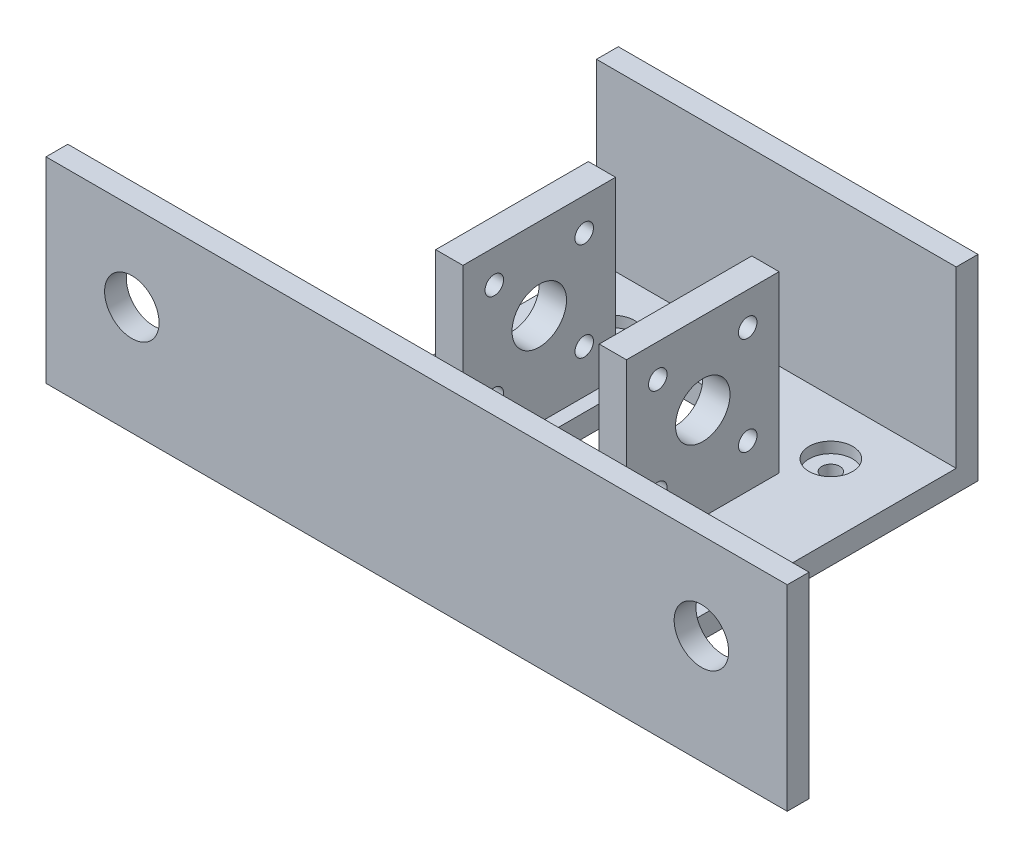
SolidWorks part; units mm, degrees
ref_plane "Front Plane" through (0, 0, 0) normal (0, 0, 1) x (1, 0, 0)
ref_plane "Top Plane" through (0, 0, 0) normal (0, 1, 0) x (1, 0, 0)
ref_plane "Right Plane" through (0, 0, 0) normal (1, 0, 0) x (0, 0, -1)
sketch "Sketch1" plane through (0, 0, 0) normal (0, 1, 0) x (1, 0, 0)
  line L0 (0, 0) -> (0, -14.43) construction
  line L1 (-37.5, 20) -> (37.5, 20)
  line L2 (-37.5, 20) -> (-37.5, -20)
  line L3 (-37.5, -20) -> (37.5, -20)
  line L4 (37.5, 20) -> (37.5, -20)
  line L5 (-37.5, 20) -> (37.5, -20) construction
  line L6 (-37.5, -20) -> (37.5, 20) construction
  line L7 (0, 0) -> (6.508, 0) construction
  line L8 (-5, 10) -> (5, 10)
  line L9 (-5, 10) -> (-5, -10)
  line L10 (-5, -10) -> (5, -10)
  line L11 (5, 10) -> (5, -10)
  line L12 (-5, 10) -> (5, -10) construction
  line L13 (-5, -10) -> (5, 10) construction
  circle A0 centre (-21, 0) radius 5
  circle A1 centre (-30, 8.25) radius 1.7
  circle A2 centre (-12, 8.25) radius 1.7
  circle A3 centre (-12, -8.25) radius 1.7
  circle A4 centre (-30, -8.25) radius 1.7
  circle A5 centre (12, 8.25) radius 1.7
  circle A6 centre (12, -8.25) radius 1.7
  circle A7 centre (21, 0) radius 5
  circle A8 centre (30, -8.25) radius 1.7
  circle A9 centre (30, 8.25) radius 1.7
  point P0 (0, 0)
  dimension "D3" = 10
  dimension "D4" = 16.5
  dimension "D5" = 16.5
  dimension "D6" = 18
  dimension "D9" = 10
  dimension "D11" = 20
  dimension "D13" = 7.5
  dimension "D17" = 3.4
  dimension "D19" = 11.75
  dimension "D20" = 11.75
  dimension "D1" = 75
  dimension "D2" = 40
  dimension "D10" = 10
  dimension "D7" = 2
  dimension "D8" = 2
extrude "Boss-Extrude1" add sketch "Sketch1" along normal blind 3
sketch "Sketch2" plane through (0, 3, 0) normal (0, 1, 0) x (1, 0, 0)
  line L0 (-37.5, 20) -> (-37.5, -20) construction
  line L1 (-33.5, 14) -> (33.5, 14)
  line L2 (-33.5, 14) -> (-33.5, -14)
  line L3 (-33.5, -14) -> (33.5, -14)
  line L4 (33.5, 14) -> (33.5, -14)
  line L5 (37.5, -20) -> (37.5, 20) construction
  line L6 (37.5, 20) -> (-37.5, 20) construction
  line L7 (-37.5, -20) -> (37.5, -20) construction
  dimension "D1" = 4
  dimension "D2" = 4
  dimension "D3" = 6
  dimension "D4" = 6
extrude "Cut-Extrude1" cut sketch "Sketch2" against normal through all both and the other way through all
sketch "Sketch3" plane through (0, 3, 0) normal (0, 1, 0) x (1, 0, 0)
  line L1 (37.5, 20) -> (-37.5, 20)
  line L2 (37.5, 20) -> (37.5, 35)
  line L3 (37.5, 35) -> (-37.5, 35)
  line L4 (-37.5, 20) -> (-37.5, 35)
  line L5 (-37.5, -20) -> (37.5, -20)
  line L6 (-37.5, -20) -> (-37.5, -35)
  line L7 (-37.5, -35) -> (37.5, -35)
  line L8 (37.5, -20) -> (37.5, -35)
  line L10 (-37.5, 20) -> (-33.5, 20)
  line L11 (-37.5, 20) -> (-37.5, -20)
  line L12 (-37.5, -20) -> (-33.5, -20)
  line L13 (-33.5, 20) -> (-33.5, -20)
  line L14 (37.5, 20) -> (33.5, 20)
  line L15 (37.5, 20) -> (37.5, -20)
  line L16 (37.5, -20) -> (33.5, -20)
  line L17 (33.5, 20) -> (33.5, -20)
  line M3 (-33.5, -14) -> (-33.5, 14)
  line M5 (33.5, 14) -> (33.5, -14)
  line M11 (37.5, -20) -> (37.5, 20)
  line M12 (37.5, 20) -> (-37.5, 20)
  line M13 (-37.5, 20) -> (-37.5, -20)
  line M14 (-37.5, -20) -> (37.5, -20)
  dimension "D1" = 15
  dimension "D2" = 15
extrude "Boss-Extrude3" add sketch "Sketch3" along normal blind 110 and the other way blind 3 contours L8 L5 L6 L7 M14 | L4 L1 L2 L3 M12 | L17 M12 M5 M14 M11 | L13 L1 M13 M14 M3 region at (35.5, 3, 0) region at (0, 3, -27.5) region at (0, 3, 27.5) region at (-35.5, 3, 0)
sketch "Sketch6" plane through (0, 3, 0) normal (0, 1, 0) x (1, 0, 0)
  line L0 (-37.5, -35) -> (37.5, -35) construction
  line L1 (-33.5, -20) -> (33.5, -20)
  line L2 (-33.5, -20) -> (-33.5, -31)
  line L3 (-33.5, -31) -> (33.5, -31)
  line L4 (33.5, -20) -> (33.5, -31)
  line L5 (33.5, 20) -> (-33.5, 20)
  line L6 (33.5, 20) -> (33.5, 31)
  line L7 (33.5, 31) -> (-33.5, 31)
  line L8 (-33.5, 20) -> (-33.5, 31)
  line L9 (37.5, 35) -> (-37.5, 35) construction
  dimension "D1" = 4
  dimension "D2" = 4
extrude "Cut-Extrude4" cut sketch "Sketch6" along normal through all
sketch "Sketch7" plane through (-37.5, 0, 0) normal (-1, 0, 0) x (0, 0, 1)
  line L0 (35, 0) -> (35, 113) construction
  line L1 (-35, 113) -> (35, 113)
  line L2 (-35, 113) -> (-35, 76)
  line L3 (-35, 76) -> (35, 76)
  line L4 (35, 113) -> (35, 76)
  dimension "D1" = 37
extrude "Boss-Extrude4" add sketch "Sketch7" along normal blind 45
ref_plane "Plane1" through (0, 0, 0) normal (1, 0, 0) x (0, 0, -1)
mirror "Mirror2" about plane through (0, 0, 0) normal (1, 0, 0) of "Boss-Extrude4"
sketch "Sketch8" plane through (0, 113, 0) normal (0, 1, 0) x (1, 0, 0)
  line L0 (-82.5, -35) -> (-82.5, 35) construction
  line L1 (-33.5, 31) -> (-78.5, 31)
  line L2 (-33.5, 31) -> (-33.5, -31)
  line L3 (-33.5, -31) -> (-78.5, -31)
  line L4 (-78.5, 31) -> (-78.5, -31)
  line L5 (33.5, -31) -> (78.5, -31)
  line L6 (33.5, -31) -> (33.5, 31)
  line L7 (33.5, 31) -> (78.5, 31)
  line L8 (78.5, -31) -> (78.5, 31)
  line L9 (82.5, -35) -> (82.5, 35) construction
  dimension "D1" = 4
  dimension "D2" = 4
extrude "Cut-Extrude6" cut sketch "Sketch8" against normal blind 29
sketch "Sketch9" plane through (-82.5, 0, 0) normal (-1, 0, 0) x (0, 0, 1)
  line L18 (-31, 84) -> (31, 84) construction
  line L19 (-19, 84) -> (19, 84)
  line L20 (-19, 84) -> (-19, 112.5)
  line L21 (-19, 112.5) -> (19, 112.5)
  line L22 (19, 84) -> (19, 112.5)
  line L25 (-31, 84) -> (-31, 113) construction
  dimension "D1" = 38
  dimension "D2" = 12
  dimension "D3" = 28.5
sketch "Sketch11" plane through (0, 0, 35) normal (0, 0, 1) x (1, 0, 0)
  line L0 (82.5, 76) -> (82.5, 113) construction
  line L1 (-82.5, 76) -> (-37.5, 76)
  line L2 (-82.5, 76) -> (-82.5, 80)
  line L3 (-82.5, 80) -> (-37.5, 80)
  line L4 (-37.5, 76) -> (-37.5, 80)
  line L5 (37.5, 76) -> (82.5, 76)
  line L6 (37.5, 76) -> (37.5, 80)
  line L7 (37.5, 80) -> (82.5, 80)
  line L8 (82.5, 76) -> (82.5, 80)
  line L11 (-78.5, 84) -> (-33.5, 84) construction
  line L12 (33.5, 84) -> (78.5, 84) construction
  dimension "D1" = 4
  dimension "D2" = 4
extrude "Cut-Extrude9" cut sketch "Sketch11" against normal through all
extrude "Cut-Extrude10" cut sketch "Sketch9" against normal through all
sketch "Sketch13" plane through (0, 84, 0) normal (0, 1, 0) x (1, 0, 0)
  line L0 (-78.5, 31) -> (-78.5, -31) construction
  line L1 (-41.5, 19) -> (-36.5, 19)
  line L2 (-41.5, 19) -> (-41.5, -19)
  line L3 (-41.5, -19) -> (-36.5, -19)
  line L4 (-36.5, 19) -> (-36.5, -19)
  line L7 (78.5, 31) -> (-78.5, 31) construction
  line L13 (-41.5, -19) -> (-41.5, 19)
  line L17 (-82.5, -19) -> (-107.5, -19)
  line L18 (-82.5, -19) -> (-82.5, 19)
  line L19 (-82.5, 19) -> (-107.5, 19)
  line L20 (-107.5, -19) -> (-107.5, 19)
  line L21 (-107.5, 19) -> (-61, 19)
  line L22 (-107.5, 19) -> (-107.5, -19)
  line L23 (-107.5, -19) -> (-61, -19)
  line L24 (-61, 19) -> (-61, -19)
  dimension "D1" = 37
  dimension "D2" = 5
  dimension "D3" = 38
  dimension "D4" = 12
  dimension "D5" = 25
  dimension "D6" = 46.5
extrude "Boss-Extrude5" add sketch "Sketch13" along normal blind 32 contours L4 L1 L2 L3 region at (-39, 84, 0)
sketch "Sketch14" plane through (-41.5, 0, 0) normal (-1, 0, 0) x (0, 0, 1)
  line L0 (-19, 116) -> (-19, 84) construction
  line L4 (19, 112.5) -> (-19, 112.5) construction
  circle A0 centre (0, 101) radius 5
  circle A1 centre (-8.25, 110) radius 1.7
  circle A2 centre (8.25, 110) radius 1.7
  circle A3 centre (8.25, 92) radius 1.7
  circle A4 centre (-8.25, 92) radius 1.7
  dimension "D1" = 19
  dimension "D2" = 8.25
  dimension "D3" = 10
  dimension "D6" = 3.4
  dimension "D7" = 11.5
  dimension "D8" = 18
  dimension "D9" = 16.5
  dimension "D10" = 9
  dimension "D11" = 8.25
  dimension "D4" = 2
  dimension "D5" = 2
extrude "Cut-Extrude11" cut sketch "Sketch14" against normal blind 32
mirror "Mirror4" about plane through (0, 0, 0) normal (1, 0, 0) of "Boss-Extrude5", "Cut-Extrude11"
sketch "Sketch15" plane through (0, 113, 0) normal (0, 1, 0) x (1, 0, 0)
  line L1 (-82.5, 35) -> (82.5, 35)
  line L2 (-82.5, 35) -> (-82.5, -35)
  line L3 (-82.5, -35) -> (82.5, -35)
  line L4 (82.5, 35) -> (82.5, -35)
  line L5 (-78.5, 31) -> (78.5, 31)
  line L6 (-78.5, 31) -> (-78.5, -31)
  line L7 (-78.5, -31) -> (78.5, -31)
  line L8 (78.5, 31) -> (78.5, -31)
extrude "Boss-Extrude6" add sketch "Sketch15" along normal blind 3
sketch "Sketch16" plane through (0, 0, 35) normal (0, 0, 1) x (1, 0, 0)
  line L1 (-10, 14.0464) -> (10, 14.0464)
  line L2 (-10, 14.0464) -> (-10, 9.2258)
  line L3 (-10, 9.2258) -> (10, 9.2258)
  line L4 (10, 14.0464) -> (10, 9.2258)
  line L5 (-37.5, 0) -> (-37.5, 80) construction
  dimension "D1" = 20
  dimension "D2" = 27.5
extrude "Cut-Extrude12" cut sketch "Sketch16" against normal through all
sketch "Sketch18" plane through (0, 0, 35) normal (0, 0, 1) x (1, 0, 0)
  line L0 (41.5, 116) -> (41.5, 84) construction
  line L2 (33.5, 84) -> (78.5, 84) construction
  circle A0 centre (52.25, 100) radius 5
  dimension "D1" = 10.75
  dimension "D2" = 16
  dimension "D3" = 10
extrude "Cut-Extrude14" cut sketch "Sketch18" against normal through all
mirror "Mirror5" about plane through (0, 0, 0) normal (1, 0, 0) of "Cut-Extrude14"
mirror "Mirror6" about plane through (0, 116, 0) normal (0, 1, 0) of "Mirror4"
sketch "Sketch19" plane through (82.5, 0, 0) normal (1, 0, 0) x (0, 0, -1)
  line L0 (19, 148) -> (19, 84) construction
  line L1 (-19, 112.5) -> (19, 112.5)
  line L2 (-19, 112.5) -> (-19, 116)
  line L3 (-19, 116) -> (19, 116)
  line L4 (19, 112.5) -> (19, 116)
extrude "Cut-Extrude15" cut sketch "Sketch19" against normal blind 10
mirror "Mirror7" about plane through (0, 0, 0) normal (1, 0, 0) of "Cut-Extrude15"
sketch "Sketch20" plane through (0, 3, 0) normal (0, 1, 0) x (1, 0, 0)
  line L0 (33.5, 31) -> (-33.5, 31) construction
  line L1 (-5, -10) -> (5, -10)
  line L2 (-5, -10) -> (-5, 10)
  line L3 (-5, 10) -> (5, 10)
  line L4 (5, -10) -> (5, 10)
  line L5 (-5, -10) -> (5, 10) construction
  line L6 (-5, 10) -> (5, -10) construction
  line L7 (0, 0) -> (0, 17.5) construction
  line L8 (-37.5, 20) -> (37.5, 20)
  line L9 (-37.5, 20) -> (-37.5, -20)
  line L10 (-37.5, -20) -> (37.5, -20)
  line L11 (37.5, 20) -> (37.5, -20)
  line L12 (-37.5, 20) -> (37.5, -20) construction
  line L13 (-37.5, -20) -> (37.5, 20) construction
  line L14 (0, -34.1) -> (0, 34.1) construction
  circle A1 centre (-12, 17.5) radius 1.2
  circle A2 centre (-12, -17.5) radius 1.2
  circle A3 centre (-24, -17.5) radius 1.2
  circle A4 centre (-24, 17.5) radius 1.2
  circle A5 centre (12, -17.5) radius 1.2
  circle A6 centre (24, -17.5) radius 1.2
  circle A7 centre (12, 17.5) radius 1.2
  circle A8 centre (24, 17.5) radius 1.2
  point P2 (0, 0)
  point P10 (0, 0)
  dimension "D1" = 7
  dimension "D2" = 10
  dimension "D4" = 2.5
  dimension "D7" = 35
  dimension "D8" = 7
  dimension "D9" = 2.4
  dimension "D11" = 12
  dimension "D3" = 21
  dimension "D5" = 75
  dimension "D6" = 40
  dimension "D10" = 2
extrude "Cut-Extrude16" cut sketch "Sketch20" against normal blind 10 contours A4 | A1 | A7 | A3 | A2 | A8 | A5 | A6 region at (-12, 3, -17.5) region at (-12, 3, 17.5) region at (-24, 3, 17.5) region at (-24, 3, -17.5) region at (12, 3, 17.5) region at (24, 3, 17.5) region at (12, 3, -17.5) region at (24, 3, -17.5)
sketch "Sketch21" plane through (0, 0, 35) normal (0, 0, 1) x (1, 0, 0)
  line L0 (0, -34.1) -> (0, 34.1) construction
  line L1 (37.5, 0) -> (27.5, 0)
  line L2 (37.5, 0) -> (37.5, 80)
  line L3 (37.5, 80) -> (27.5, 80)
  line L4 (27.5, 0) -> (27.5, 80)
  line L5 (-27.5, 0) -> (-27.5, 80)
  line L6 (-37.5, 80) -> (-27.5, 80)
  line L7 (-37.5, 0) -> (-37.5, 80)
  line L8 (-37.5, 0) -> (-27.5, 0)
  dimension "D1" = 10
  dimension "D2" = 80
extrude "Cut-Extrude17" cut sketch "Sketch21" against normal through all
sketch "Sketch22" plane through (0, 0, 35) normal (0, 0, 1) x (1, 0, 0)
  line L1 (-27.5, 0) -> (27.5, 0)
  line L2 (-27.5, 0) -> (-27.5, 80)
  line L3 (-27.5, 80) -> (27.5, 80)
  line L4 (27.5, 0) -> (27.5, 80)
extrude "Cut-Extrude18" cut sketch "Sketch22" against normal through all
sketch "Sketch23" plane through (0, 80, 0) normal (0, -1, 0) x (1, 0, 0)
  line L1 (-33.5, 31) -> (33.5, 31)
  line L2 (-33.5, 31) -> (-33.5, -31)
  line L3 (-33.5, -31) -> (33.5, -31)
  line L4 (33.5, 31) -> (33.5, -31)
extrude "Boss-Extrude7" add sketch "Sketch23" against normal blind 4
sketch "Sketch24" plane through (0, 84, 0) normal (0, 1, 0) x (1, 0, 0)
  line L10 (0, 0) -> (0, 16.8876) construction
  line L11 (0, -34.1) -> (0, 34.1) construction
  circle A0 centre (0, 0) radius 10
  circle A1 centre (-20, 21) radius 1.65
  circle A2 centre (-20, -21) radius 1.65
  circle A3 centre (20, -21) radius 1.65
  circle A4 centre (20, 21) radius 1.65
  dimension "D1" = 20
  dimension "D2" = 21
  dimension "D3" = 20
  dimension "D4" = 21
  dimension "D5" = 3.3
  dimension "D6" = 3.3
extrude "Cut-Extrude19" cut sketch "Sketch24" against normal through all
sketch "Sketch25" plane through (0, 0, -35) normal (0, 0, -1) x (-1, 0, 0)
  line L0 (33.5, 84) -> (33.5, 80)
  line L5 (-82.5, 80) -> (82.5, 80) construction
  line L7 (33.5, 80) -> (82.5, 80)
  line L8 (33.5, 80) -> (33.5, 116)
  line L9 (33.5, 116) -> (82.5, 116)
  line L10 (82.5, 80) -> (82.5, 116)
  line M2 (-82.5, 80) -> (82.5, 80)
  line M3 (82.5, 80) -> (82.5, 116)
  line M4 (82.5, 116) -> (-82.5, 116)
  circle M5 centre (52.25, 100) radius 5
extrude "Cut-Extrude21" cut sketch "Sketch25" against normal blind 16 contours L8 L0 M2 M3 M4 M5 region at (-58.2679, 97.9068, -35)
mirror "Mirror8" about plane through (0, 0, 0) normal (1, 0, 0) of "Cut-Extrude21"
sketch "Sketch26" plane through (0, 0, -19) normal (0, 0, -1) x (-1, 0, 0)
  line L0 (78.5, 116) -> (-78.5, 116) construction
  line L1 (82.5, 80) -> (68, 80)
  line L2 (82.5, 80) -> (82.5, 116)
  line L3 (82.5, 116) -> (68, 116)
  line L4 (68, 80) -> (68, 116)
  dimension "D1" = 14.5
extrude "Cut-Extrude22" cut sketch "Sketch26" against normal through all
mirror "Mirror9" about plane through (0, 0, 0) normal (1, 0, 0) of "Cut-Extrude22"
sketch "Sketch27" plane through (0, 0, -19) normal (0, 0, -1) x (-1, 0, 0)
  line L1 (-41.5, 148) -> (-36.5, 148)
  line L2 (-41.5, 148) -> (-41.5, 84)
  line L3 (-41.5, 84) -> (-36.5, 84)
  line L4 (-36.5, 148) -> (-36.5, 84)
extrude "Cut-Extrude23" cut sketch "Sketch27" against normal blind 43
sketch "Sketch28" plane through (0, 84, 0) normal (0, 1, 0) x (1, 0, 0)
  line L5 (-68, -31) -> (68, -31) construction
  line L6 (68, 19) -> (33.5, 19)
  line L7 (68, 19) -> (68, -31)
  line L8 (68, -31) -> (33, -31)
  line L9 (33, 19) -> (33, -31)
  line L11 (33.5, 35) -> (33, 35)
  line L12 (33.5, 35) -> (33.5, 19)
  line L14 (33, 35) -> (33, 19)
  dimension "D1" = 0
  dimension "D2" = 35
extrude "Cut-Extrude24" cut sketch "Sketch28" against normal through all both and the other way through all
sketch "Sketch29" plane through (0, 84, 0) normal (0, 1, 0) x (1, 0, 0)
  line L0 (0, -34.1) -> (0, 34.1) construction
  line L2 (0, 0) -> (13.2142, 0)
  circle A0 centre (-20, 21) radius 4
  circle A1 centre (20, 21) radius 4
  circle A2 centre (20, -21) radius 4
  circle A3 centre (-20, -21) radius 4
  circle M12 centre (20, 21) radius 1.65
  circle M13 centre (20, -21) radius 1.65
  circle M14 centre (-20, 21) radius 1.65
  circle M15 centre (-20, -21) radius 1.65
extrude "Cut-Extrude25" cut sketch "Sketch29" against normal blind 2 contours A1 M12 | A0 M14 | A3 M15 | A2 M13 region at (-23.8869, 84, -21) region at (16.1131, 84, -21) region at (16.1131, 84, 21) region at (-23.8869, 84, 21)
sketch "Sketch30" plane through (0, 84, 0) normal (0, 1, 0) x (1, 0, 0)
  line L1 (0, -34.1) -> (0, 34.1) construction
  line L3 (12.5, -14) -> (17.5, -14)
  line L4 (12.5, -14) -> (12.5, 14)
  line L5 (12.5, 14) -> (17.5, 14)
  line L6 (17.5, -14) -> (17.5, 14)
  line L8 (-68, -31) -> (68, -31) construction
  line L9 (33, 31) -> (-33.5, 31) construction
  point P6 (0, 0)
  dimension "D1" = 12.5
  dimension "D2" = 5
  dimension "D3" = 17
  dimension "D4" = 17
extrude "Boss-Extrude8" add sketch "Sketch30" along normal blind 32
sketch "Sketch32" plane through (17.5, 0, 0) normal (1, 0, 0) x (0, 0, -1)
  circle A0 centre (0, 101) radius 5
  circle A1 centre (8.25, 110) radius 1.7
  circle A2 centre (-8.25, 110) radius 1.7
  circle A3 centre (-8.25, 92) radius 1.7
  circle A4 centre (8.25, 92) radius 1.7
  dimension "D1" = 2
  dimension "D2" = 2
extrude "Cut-Extrude26" cut sketch "Sketch32" against normal blind 32
mirror "Mirror11" about plane through (0, 0, 0) normal (1, 0, 0) of "Cut-Extrude24"
mirror "Mirror16" about plane through (0, 0, 0) normal (1, 0, 0) of "Boss-Extrude8"
mirror "Mirror18" about plane through (0, 0, 0) normal (1, 0, 0) of "Cut-Extrude26"
sketch "Sketch34" plane through (0, 84, 0) normal (0, 1, 0) x (1, 0, 0)
  line L1 (-10, 0) -> (10, 0)
  line L2 (-10, 0) -> (-10, 21)
  line L3 (-10, 21) -> (10, 21)
  line L4 (10, 0) -> (10, 21)
  line L5 (-10, 0) -> (10, 0)
  line L6 (-10, 0) -> (-10, -21)
  line L7 (-10, -21) -> (10, -21)
  line L8 (10, 0) -> (10, -21)
  circle A0 centre (0, 0) radius 10 construction
  circle M13 centre (0, 0) radius 10
  dimension "D1" = 21
  dimension "D2" = 21
extrude "Cut-Extrude27" cut sketch "Sketch34" against normal blind 32 contours L4 L3 L2 M13 | L8 L6 L7 M13 region at (0, 84, 14.2375) region at (0, 84, -14.2375)
